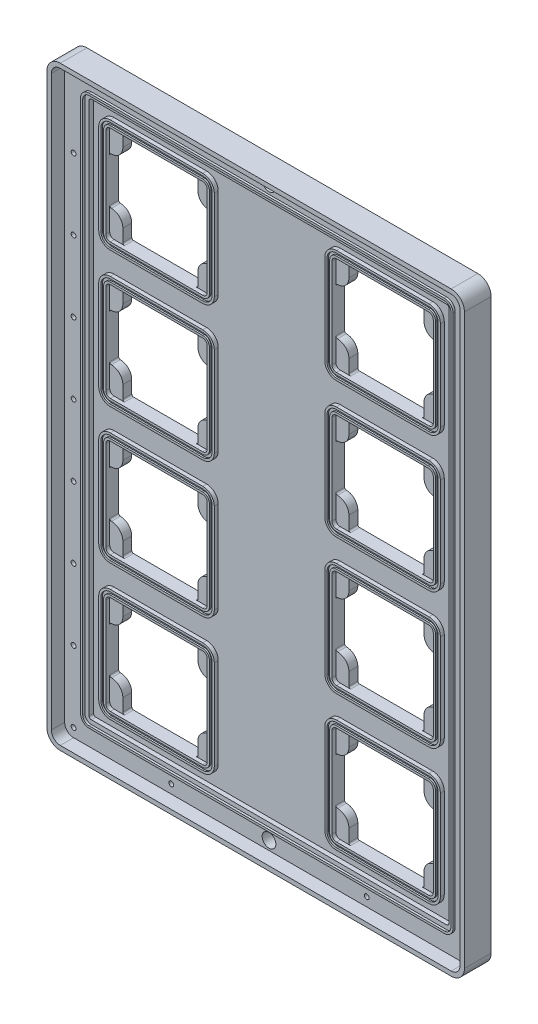
SolidWorks part; units mm, degrees
ref_plane "Front Plane" through (0, 0, 0) normal (0, 0, 1) x (1, 0, 0)
ref_plane "Top Plane" through (0, 0, 0) normal (0, 1, 0) x (1, 0, 0)
ref_plane "Right Plane" through (0, 0, 0) normal (1, 0, 0) x (0, 0, -1)
sketch "Sketch1" plane through (0, 0, 0) normal (0, 0, 1) x (1, 0, 0)
  line L1 (0, 0) -> (292.1, 0)
  line L2 (0, 0) -> (0, 419.1)
  line L3 (0, 419.1) -> (292.1, 419.1)
  line L4 (292.1, 0) -> (292.1, 419.1)
  dimension "D1" = 419.1
  dimension "D2" = 292.1
extrude "Boss-Extrude1" add sketch "Sketch1" along normal blind 9.525
sketch "Sketch4" plane through (0, 0, 9.525) normal (0, 0, 1) x (1, 0, 0)
  line L3 (0, 419.1) -> (0, 0) construction
  line L4 (6.35, 412.75) -> (285.75, 412.75) construction
  line L5 (6.35, 412.75) -> (6.35, 6.35) construction
  line L6 (6.35, 6.35) -> (285.75, 6.35) construction
  line L7 (285.75, 412.75) -> (285.75, 6.35) construction
  line L8 (292.1, 419.1) -> (0, 419.1) construction
  line L9 (292.1, 0) -> (292.1, 419.1) construction
  line L10 (0, 0) -> (292.1, 0) construction
  circle A0 centre (6.35, 6.35) radius 1.7272
  circle A1 centre (6.35, 412.75) radius 1.7272
  circle A2 centre (285.75, 412.75) radius 1.7272
  circle A3 centre (285.75, 6.35) radius 1.7272
  dimension "D5" = 3.4544
  dimension "D1" = 6.35
  dimension "D2" = 6.35
  dimension "D3" = 6.35
  dimension "D4" = 6.35
extrude "Cut-Extrude1" cut sketch "Sketch4" against normal blind 6.985
pattern_linear "LPattern2" count 8 spacing 50.8 along (0, -1, 0) of "Cut-Extrude1"
pattern_linear "LPattern3" count 4 spacing 69.85 along (-1, 0, 0) of "Cut-Extrude1"
sketch "Sketch5" plane through (0, 0, 9.525) normal (0, 0, 1) x (1, 0, 0)
  line L0 (0, 419.1) -> (0, 0) construction
  line L1 (19.05, 406.4) -> (273.05, 406.4) construction
  line L2 (12.7, 400.05) -> (12.7, 19.05) construction
  line L3 (19.05, 12.7) -> (273.05, 12.7) construction
  line L4 (279.4, 400.05) -> (279.4, 19.05) construction
  line L5 (292.1, 419.1) -> (0, 419.1) construction
  line L6 (292.1, 0) -> (292.1, 419.1) construction
  line L7 (0, 0) -> (292.1, 0) construction
  line L8 (19.05, 14.732) -> (273.05, 14.732) construction
  line L9 (14.732, 400.05) -> (14.732, 19.05) construction
  line L10 (19.05, 404.368) -> (273.05, 404.368) construction
  line L11 (277.368, 400.05) -> (277.368, 19.05) construction
  line L12 (12.954, 400.05) -> (12.954, 19.05)
  line L13 (19.05, 406.146) -> (273.05, 406.146)
  line L14 (279.146, 400.05) -> (279.146, 19.05)
  line L15 (19.05, 12.954) -> (273.05, 12.954)
  line L16 (277.622, 400.05) -> (277.622, 19.05)
  line L17 (19.05, 404.622) -> (273.05, 404.622)
  line L18 (14.478, 400.05) -> (14.478, 19.05)
  line L19 (19.05, 14.478) -> (273.05, 14.478)
  arc A0 (273.05, 12.7) -> (279.4, 19.05) centre (273.05, 19.05) ccw construction
  arc A1 (12.7, 19.05) -> (19.05, 12.7) centre (19.05, 19.05) ccw construction
  arc A2 (273.05, 406.4) -> (279.4, 400.05) centre (273.05, 400.05) cw construction
  arc A3 (19.05, 406.4) -> (12.7, 400.05) centre (19.05, 400.05) ccw construction
  arc A4 (14.732, 19.05) -> (19.05, 14.732) centre (19.05, 19.05) ccw construction
  arc A5 (19.05, 404.368) -> (14.732, 400.05) centre (19.05, 400.05) ccw construction
  arc A6 (273.05, 404.368) -> (277.368, 400.05) centre (273.05, 400.05) cw construction
  arc A7 (273.05, 14.732) -> (277.368, 19.05) centre (273.05, 19.05) ccw construction
  arc A8 (19.05, 406.146) -> (12.954, 400.05) centre (19.05, 400.05) ccw
  arc A9 (273.05, 406.146) -> (279.146, 400.05) centre (273.05, 400.05) cw
  arc A10 (273.05, 12.954) -> (279.146, 19.05) centre (273.05, 19.05) ccw
  arc A11 (12.954, 19.05) -> (19.05, 12.954) centre (19.05, 19.05) ccw
  arc A12 (273.05, 404.622) -> (277.622, 400.05) centre (273.05, 400.05) cw
  arc A13 (19.05, 404.622) -> (14.478, 400.05) centre (19.05, 400.05) ccw
  arc A14 (14.478, 19.05) -> (19.05, 14.478) centre (19.05, 19.05) ccw
  arc A15 (273.05, 14.478) -> (277.622, 19.05) centre (273.05, 19.05) ccw
  dimension "D5" = 6.35
  dimension "D1" = 12.7
  dimension "D2" = 12.7
  dimension "D3" = 12.7
  dimension "D4" = 12.7
  dimension "D6" = 2.032
  dimension "D7" = 2.032
  dimension "D8" = 0.254
  dimension "D9" = 0.254
  dimension "D10" = 0.254
sketch "Sketch6" plane through (0, 0, 9.525) normal (0, 0, 1) x (1, 0, 0)
  line L0 (292.1, 419.1) -> (0, 419.1) construction
  line L1 (0, 419.1) -> (0, 0) construction
  line L24 (273.05, 401.6375) -> (19.05, 401.6375)
  line L25 (274.6375, 19.05) -> (274.6375, 400.05)
  line L26 (19.05, 17.4625) -> (273.05, 17.4625)
  line L27 (17.4625, 400.05) -> (17.4625, 19.05)
  line L28 (273.05, 401.6375) -> (19.05, 401.6375)
  line L29 (274.6375, 19.05) -> (274.6375, 400.05)
  line L30 (19.05, 17.4625) -> (273.05, 17.4625)
  line L31 (17.4625, 400.05) -> (17.4625, 19.05)
  arc A20 (19.05, 401.6375) -> (17.4625, 400.05) centre (19.05, 400.05) ccw
  arc A21 (274.6375, 400.05) -> (273.05, 401.6375) centre (273.05, 400.05) ccw
  arc A22 (273.05, 17.4625) -> (274.6375, 19.05) centre (273.05, 19.05) ccw
  arc A23 (17.4625, 19.05) -> (19.05, 17.4625) centre (19.05, 19.05) ccw
  arc A24 (19.05, 401.6375) -> (17.4625, 400.05) centre (19.05, 400.05) ccw
  arc A25 (274.6375, 400.05) -> (273.05, 401.6375) centre (273.05, 400.05) ccw
  arc A26 (273.05, 17.4625) -> (274.6375, 19.05) centre (273.05, 19.05) ccw
  arc A27 (17.4625, 19.05) -> (19.05, 17.4625) centre (19.05, 19.05) ccw
  dimension "D2" = 17.4625
  dimension "D3" = 17.4625
  dimension "D1" = 2.7305
extrude "Cut-Extrude3" cut sketch "Sketch6" against normal blind 3.175
extrude "Boss-Extrude2" add sketch "Sketch5" along normal blind 1.5875 contours L12 A11 L15 A10 L14 A9 L13 A8 A15 L19 A14 L18 A13 L17 A12 L16 region at (15.0752, 404.0248, 9.525)
sketch "Sketch7" plane through (0, 0, 9.525) normal (0, 0, 1) x (1, 0, 0)
  circle A0 centre (146.05, 6.35) radius 4.9022
  circle A1 centre (146.05, 412.75) radius 4.9022
  dimension "D1" = 9.8044
extrude "Cut-Extrude4" cut sketch "Sketch7" against normal through all
fillet "Fillet1" radius 6.35 4 edges at (0, 419.1, 4.7625) (292.1, 419.1, 4.7625) (0, 0, 4.7625) (292.1, 0, 4.7625)
sketch "Sketch8" plane through (0, 0, 0) normal (0, 0, -1) x (-1, 0, 0)
  line L0 (-264.668, 370.459) -> (-264.668, 339.2678)
  line L1 (-255.27, 329.8698) -> (-255.27, 320.8782)
  line L2 (-252.4506, 318.0588) -> (-201.2442, 318.0588)
  line L3 (-198.4248, 320.8782) -> (-198.4248, 329.8698)
  line L4 (-189.0268, 339.2678) -> (-189.0268, 370.459)
  line L5 (-198.4248, 379.857) -> (-198.4248, 388.8486)
  line L6 (-201.2442, 391.668) -> (-252.4506, 391.668)
  line L7 (-255.27, 388.8486) -> (-255.27, 379.857)
  line L8 (-261.8486, 391.668) -> (-261.8486, 318.0588) construction
  line L9 (-264.668, 388.8486) -> (-189.0268, 388.8486) construction
  line L10 (-264.668, 391.668) -> (-189.0268, 391.668) construction
  line L11 (-264.668, 391.668) -> (-264.668, 318.0588) construction
  line L12 (-264.668, 318.0588) -> (-189.0268, 318.0588) construction
  line L13 (-189.0268, 391.668) -> (-189.0268, 318.0588) construction
  line L14 (-264.668, 379.857) -> (-189.0268, 379.857) construction
  line L15 (-264.668, 370.459) -> (-189.0268, 370.459) construction
  line L16 (-264.668, 339.2678) -> (-189.0268, 339.2678) construction
  line L17 (-264.668, 329.8698) -> (-189.0268, 329.8698) construction
  line L18 (-264.668, 320.8782) -> (-189.0268, 320.8782) construction
  line L19 (-255.27, 318.0588) -> (-255.27, 391.668) construction
  line L20 (-252.4506, 391.668) -> (-252.4506, 318.0588) construction
  line L21 (-201.2442, 391.668) -> (-201.2442, 318.0588) construction
  line L22 (-198.4248, 391.668) -> (-198.4248, 318.0588) construction
  line L23 (-191.8462, 318.0588) -> (-191.8462, 391.668) construction
  line L24 (-189.0268, 373.2784) -> (-264.668, 373.2784) construction
  line L27 (-201.2442, 393.7) -> (-252.4506, 393.7)
  line L28 (-257.302, 388.8486) -> (-257.302, 379.857)
  line L29 (-266.7, 370.459) -> (-266.7, 339.2678)
  line L30 (-257.302, 329.8698) -> (-257.302, 320.8782)
  line L31 (-252.4506, 316.0268) -> (-201.2442, 316.0268)
  line L32 (-196.3928, 320.8782) -> (-196.3928, 329.8698)
  line L33 (-186.9948, 339.2678) -> (-186.9948, 370.459)
  line L34 (-196.3928, 379.857) -> (-196.3928, 388.8486)
  line L35 (-285.75, 419.1) -> (-6.35, 419.1) construction
  line L36 (-292.1, 6.35) -> (-292.1, 412.75) construction
  arc A0 (-261.8486, 373.2784) -> (-255.27, 379.857) centre (-261.8486, 379.857) ccw
  arc A1 (-261.8486, 373.2784) -> (-264.668, 370.459) centre (-261.8486, 370.459) ccw
  arc A2 (-264.668, 339.2678) -> (-261.8486, 336.4484) centre (-261.8486, 339.2678) ccw
  arc A3 (-255.27, 329.8698) -> (-261.8486, 336.4484) centre (-261.8486, 329.8698) ccw
  arc A4 (-255.27, 320.8782) -> (-252.4506, 318.0588) centre (-252.4506, 320.8782) ccw
  arc A5 (-201.2442, 318.0588) -> (-198.4248, 320.8782) centre (-201.2442, 320.8782) ccw
  arc A6 (-191.8462, 336.4484) -> (-198.4248, 329.8698) centre (-191.8462, 329.8698) ccw
  arc A7 (-191.8462, 336.4484) -> (-189.0268, 339.2678) centre (-191.8462, 339.2678) ccw
  arc A8 (-189.0268, 370.459) -> (-191.8462, 373.2784) centre (-191.8462, 370.459) ccw
  arc A9 (-198.4248, 379.857) -> (-191.8462, 373.2784) centre (-191.8462, 379.857) ccw
  arc A10 (-198.4248, 388.8486) -> (-201.2442, 391.668) centre (-201.2442, 388.8486) ccw
  arc A11 (-252.4506, 391.668) -> (-255.27, 388.8486) centre (-252.4506, 388.8486) ccw
  arc A12 (-252.4506, 393.7) -> (-257.302, 388.8486) centre (-252.4506, 388.8486) ccw
  arc A13 (-261.8486, 375.3104) -> (-257.302, 379.857) centre (-261.8486, 379.857) ccw
  arc A14 (-261.8486, 375.3104) -> (-266.7, 370.459) centre (-261.8486, 370.459) ccw
  arc A15 (-266.7, 339.2678) -> (-261.8486, 334.4164) centre (-261.8486, 339.2678) ccw
  arc A16 (-257.302, 329.8698) -> (-261.8486, 334.4164) centre (-261.8486, 329.8698) ccw
  arc A17 (-257.302, 320.8782) -> (-252.4506, 316.0268) centre (-252.4506, 320.8782) ccw
  arc A18 (-201.2442, 316.0268) -> (-196.3928, 320.8782) centre (-201.2442, 320.8782) ccw
  arc A19 (-191.8462, 334.4164) -> (-196.3928, 329.8698) centre (-191.8462, 329.8698) ccw
  arc A20 (-191.8462, 334.4164) -> (-186.9948, 339.2678) centre (-191.8462, 339.2678) ccw
  arc A21 (-186.9948, 370.459) -> (-191.8462, 375.3104) centre (-191.8462, 370.459) ccw
  arc A22 (-196.3928, 379.857) -> (-191.8462, 375.3104) centre (-191.8462, 379.857) ccw
  arc A23 (-196.3928, 388.8486) -> (-201.2442, 393.7) centre (-201.2442, 388.8486) ccw
  dimension "D4" = 11.811
  dimension "D5" = 21.209
  dimension "D6" = 52.4002
  dimension "D1" = 73.6092
  dimension "D2" = 75.6412
  dimension "D3" = 2.8194
  dimension "D7" = 61.7982
  dimension "D8" = 70.7898
  dimension "D9" = 2.8194
  dimension "D10" = 9.398
  dimension "D11" = 12.2174
  dimension "D12" = 63.4238
  dimension "D13" = 66.2432
  dimension "D14" = 72.8218
  dimension "D15" = 55.2196
  dimension "D16" = 25.4
  dimension "D17" = 25.4
  dimension "D18" = 2.032
extrude "Cut-Extrude5" cut sketch "Sketch8" against normal blind 3.175
sketch "Sketch10" plane through (0, 0, 0) normal (0, 0, -1) x (-1, 0, 0)
  line L18 (-263.0805, 370.459) -> (-263.0805, 339.2678)
  line L19 (-253.6825, 329.8698) -> (-253.6825, 320.8782)
  line L20 (-252.4506, 319.6463) -> (-201.2442, 319.6463)
  line L21 (-200.0123, 320.8782) -> (-200.0123, 329.8698)
  line L22 (-190.6143, 339.2678) -> (-190.6143, 370.459)
  line L23 (-200.0123, 379.857) -> (-200.0123, 388.8486)
  line L24 (-201.2442, 390.0805) -> (-252.4506, 390.0805)
  line L25 (-253.6825, 388.8486) -> (-253.6825, 379.857)
  line L26 (-263.0805, 370.459) -> (-263.0805, 339.2678)
  line L27 (-253.6825, 329.8698) -> (-253.6825, 320.8782)
  line L28 (-252.4506, 319.6463) -> (-201.2442, 319.6463)
  line L29 (-200.0123, 320.8782) -> (-200.0123, 329.8698)
  line L30 (-190.6143, 339.2678) -> (-190.6143, 370.459)
  line L31 (-200.0123, 379.857) -> (-200.0123, 388.8486)
  line L32 (-201.2442, 390.0805) -> (-252.4506, 390.0805)
  line L33 (-253.6825, 388.8486) -> (-253.6825, 379.857)
  arc A28 (-261.8486, 371.6909) -> (-263.0805, 370.459) centre (-261.8486, 370.459) ccw
  arc A29 (-263.0805, 339.2678) -> (-261.8486, 338.0359) centre (-261.8486, 339.2678) ccw
  arc A30 (-253.6825, 329.8698) -> (-261.8486, 338.0359) centre (-261.8486, 329.8698) ccw
  arc A31 (-253.6825, 320.8782) -> (-252.4506, 319.6463) centre (-252.4506, 320.8782) ccw
  arc A32 (-201.2442, 319.6463) -> (-200.0123, 320.8782) centre (-201.2442, 320.8782) ccw
  arc A33 (-191.8462, 338.0359) -> (-200.0123, 329.8698) centre (-191.8462, 329.8698) ccw
  arc A34 (-191.8462, 338.0359) -> (-190.6143, 339.2678) centre (-191.8462, 339.2678) ccw
  arc A35 (-190.6143, 370.459) -> (-191.8462, 371.6909) centre (-191.8462, 370.459) ccw
  arc A36 (-200.0123, 379.857) -> (-191.8462, 371.6909) centre (-191.8462, 379.857) ccw
  arc A37 (-200.0123, 388.8486) -> (-201.2442, 390.0805) centre (-201.2442, 388.8486) ccw
  arc A38 (-252.4506, 390.0805) -> (-253.6825, 388.8486) centre (-252.4506, 388.8486) ccw
  arc A39 (-261.8486, 371.6909) -> (-253.6825, 379.857) centre (-261.8486, 379.857) ccw
  arc A40 (-261.8486, 371.6909) -> (-263.0805, 370.459) centre (-261.8486, 370.459) ccw
  arc A41 (-263.0805, 339.2678) -> (-261.8486, 338.0359) centre (-261.8486, 339.2678) ccw
  arc A42 (-253.6825, 329.8698) -> (-261.8486, 338.0359) centre (-261.8486, 329.8698) ccw
  arc A43 (-253.6825, 320.8782) -> (-252.4506, 319.6463) centre (-252.4506, 320.8782) ccw
  arc A44 (-201.2442, 319.6463) -> (-200.0123, 320.8782) centre (-201.2442, 320.8782) ccw
  arc A45 (-191.8462, 338.0359) -> (-200.0123, 329.8698) centre (-191.8462, 329.8698) ccw
  arc A46 (-191.8462, 338.0359) -> (-190.6143, 339.2678) centre (-191.8462, 339.2678) ccw
  arc A47 (-190.6143, 370.459) -> (-191.8462, 371.6909) centre (-191.8462, 370.459) ccw
  arc A48 (-200.0123, 379.857) -> (-191.8462, 371.6909) centre (-191.8462, 379.857) ccw
  arc A49 (-200.0123, 388.8486) -> (-201.2442, 390.0805) centre (-201.2442, 388.8486) ccw
  arc A50 (-252.4506, 390.0805) -> (-253.6825, 388.8486) centre (-252.4506, 388.8486) ccw
  arc A51 (-261.8486, 371.6909) -> (-253.6825, 379.857) centre (-261.8486, 379.857) ccw
  dimension "D1" = 1.5875
extrude "Cut-Extrude6" cut sketch "Sketch10" against normal through all
sketch "Sketch11" plane through (0, 0, 0) normal (0, 0, -1) x (-1, 0, 0)
  line L0 (-226.8474, 388.8994) -> (-226.8474, 393.7) construction
  line L1 (-261.8486, 388.8994) -> (-191.8462, 388.8994) construction
  line L2 (-261.8486, 388.8994) -> (-261.8486, 320.8274) construction
  line L3 (-261.8486, 320.8274) -> (-191.8462, 320.8274) construction
  line L4 (-191.8462, 388.8994) -> (-191.8462, 320.8274) construction
  line L5 (-201.2442, 393.7) -> (-252.4506, 393.7) construction
  line L6 (-226.8474, 320.8274) -> (-226.8474, 316.0268) construction
  line L7 (-252.4506, 316.0268) -> (-201.2442, 316.0268) construction
  line L8 (-261.8486, 354.8634) -> (-266.7, 354.8634) construction
  line L9 (-266.7, 370.459) -> (-266.7, 339.2678) construction
  line L10 (-191.8462, 354.8634) -> (-186.9948, 354.8634) construction
  line L11 (-186.9948, 339.2678) -> (-186.9948, 370.459) construction
  circle A0 centre (-261.8486, 388.8994) radius 1.1303
  circle A1 centre (-191.8462, 388.8994) radius 1.1303
  circle A2 centre (-191.8462, 320.8274) radius 1.1303
  circle A3 centre (-261.8486, 320.8274) radius 1.1303
  dimension "D3" = 2.2606
  dimension "D1" = 70.0024
  dimension "D2" = 68.072
extrude "Cut-Extrude7" cut sketch "Sketch11" against normal blind 3.9688
sketch "Sketch12" plane through (0, 0, 6.35) normal (0, 0, 1) x (1, 0, 0)
  line L0 (252.4506, 390.0805) -> (201.2442, 390.0805) construction
  line L1 (193.7893, 390.0805) -> (259.9055, 390.0805)
  line L2 (190.6143, 386.9055) -> (190.6143, 322.8213)
  line L3 (193.7893, 319.6463) -> (259.9055, 319.6463)
  line L4 (263.0805, 386.9055) -> (263.0805, 322.8213)
  line L5 (263.0805, 339.2678) -> (263.0805, 370.459) construction
  line L10 (193.7893, 391.668) -> (259.9055, 391.668)
  line L11 (264.668, 386.9055) -> (264.668, 322.8213)
  line L12 (193.7893, 318.0588) -> (259.9055, 318.0588)
  line L13 (189.0268, 386.9055) -> (189.0268, 322.8213)
  line L14 (187.1218, 386.9055) -> (187.1218, 322.8213)
  line L15 (193.7893, 316.1538) -> (259.9055, 316.1538)
  line L16 (266.573, 386.9055) -> (266.573, 322.8213)
  line L17 (193.7893, 393.573) -> (259.9055, 393.573)
  line L18 (185.5343, 386.9055) -> (185.5343, 322.8213)
  line L19 (193.7893, 314.5663) -> (259.9055, 314.5663)
  line L20 (268.1605, 386.9055) -> (268.1605, 322.8213)
  line L21 (193.7893, 395.1605) -> (259.9055, 395.1605)
  line L22 (201.2442, 319.6463) -> (252.4506, 319.6463) construction
  line L23 (190.6143, 370.459) -> (190.6143, 339.2678) construction
  arc A0 (259.9055, 319.6463) -> (263.0805, 322.8213) centre (259.9055, 322.8213) ccw
  arc A1 (190.6143, 322.8213) -> (193.7893, 319.6463) centre (193.7893, 322.8213) ccw
  arc A2 (259.9055, 390.0805) -> (263.0805, 386.9055) centre (259.9055, 386.9055) cw
  arc A3 (193.7893, 390.0805) -> (190.6143, 386.9055) centre (193.7893, 386.9055) ccw
  arc A4 (259.9055, 391.668) -> (264.668, 386.9055) centre (259.9055, 386.9055) cw
  arc A5 (259.9055, 318.0588) -> (264.668, 322.8213) centre (259.9055, 322.8213) ccw
  arc A6 (189.0268, 322.8213) -> (193.7893, 318.0588) centre (193.7893, 322.8213) ccw
  arc A7 (193.7893, 391.668) -> (189.0268, 386.9055) centre (193.7893, 386.9055) ccw
  arc A8 (187.1218, 322.8213) -> (193.7893, 316.1538) centre (193.7893, 322.8213) ccw
  arc A9 (259.9055, 316.1538) -> (266.573, 322.8213) centre (259.9055, 322.8213) ccw
  arc A10 (259.9055, 393.573) -> (266.573, 386.9055) centre (259.9055, 386.9055) cw
  arc A11 (193.7893, 393.573) -> (187.1218, 386.9055) centre (193.7893, 386.9055) ccw
  arc A12 (185.5343, 322.8213) -> (193.7893, 314.5663) centre (193.7893, 322.8213) ccw
  arc A13 (259.9055, 314.5663) -> (268.1605, 322.8213) centre (259.9055, 322.8213) ccw
  arc A14 (259.9055, 395.1605) -> (268.1605, 386.9055) centre (259.9055, 386.9055) cw
  arc A15 (193.7893, 395.1605) -> (185.5343, 386.9055) centre (193.7893, 386.9055) ccw
  dimension "D1" = 3.175
  dimension "D2" = 1.5875
  dimension "D3" = 1.905
  dimension "D4" = 1.5875
extrude "Boss-Extrude3" add sketch "Sketch12" along normal blind 2.794 contours L21 A15 L18 A12 L19 A13 L20 A14 A11 L17 A10 L16 A9 L15 A8 L14 | L10 A7 L13 A6 L12 A5 L11 A4 A3 L1 A2 L4 A0 L3 A1 L2 region at (226.8474, 390.6125, 6.35) region at (188.7683, 391.9265, 6.35)
extrude "Boss-Extrude4" add sketch "Sketch12<3>" along normal blind 1.651 contours L17 A11 L14 A8 L15 A9 L16 A10 A7 L10 A4 L11 A5 L12 A6 L13 region at (189.8591, 390.8357, 6.35)
sketch "Sketch12<3>" plane through (0, 0, 6.35) normal (0, 0, 1) x (1, 0, 0) same geometry as "Sketch12"
pattern_linear "LPattern1" count 2 spacing 161.5948 along (-1, 0, 0) count 4 spacing 96.8756 along (0, -1, 0) of "Cut-Extrude6", "Cut-Extrude5", "Cut-Extrude7", "Boss-Extrude3", "Boss-Extrude4"
sketch "Sketch13" plane through (0, 0, 0) normal (0, 0, -1) x (-1, 0, 0)
  line L4 (-6.35, 419.1) -> (-285.75, 419.1)
  line L5 (-292.1, 412.75) -> (-292.1, 6.35)
  line L6 (-285.75, 0) -> (-6.35, 0)
  line L7 (0, 6.35) -> (0, 412.75)
  line L8 (-285.75, -3.175) -> (-6.35, -3.175)
  line L9 (3.175, 6.35) -> (3.175, 412.75)
  line L10 (-6.35, 422.275) -> (-285.75, 422.275)
  line L11 (-295.275, 412.75) -> (-295.275, 6.35)
  line L12 (-285.75, -3.175) -> (-6.35, -3.175)
  line L13 (3.175, 6.35) -> (3.175, 412.75)
  line L14 (-6.35, 422.275) -> (-285.75, 422.275)
  line L15 (-295.275, 412.75) -> (-295.275, 6.35)
  arc A4 (-285.75, 419.1) -> (-292.1, 412.75) centre (-285.75, 412.75) ccw
  arc A5 (-292.1, 6.35) -> (-285.75, 0) centre (-285.75, 6.35) ccw
  arc A6 (-6.35, 0) -> (0, 6.35) centre (-6.35, 6.35) ccw
  arc A7 (0, 412.75) -> (-6.35, 419.1) centre (-6.35, 412.75) ccw
  arc A8 (-295.275, 6.35) -> (-285.75, -3.175) centre (-285.75, 6.35) ccw
  arc A9 (-6.35, -3.175) -> (3.175, 6.35) centre (-6.35, 6.35) ccw
  arc A10 (3.175, 412.75) -> (-6.35, 422.275) centre (-6.35, 412.75) ccw
  arc A11 (-285.75, 422.275) -> (-295.275, 412.75) centre (-285.75, 412.75) ccw
  arc A12 (-295.275, 6.35) -> (-285.75, -3.175) centre (-285.75, 6.35) ccw
  arc A13 (-6.35, -3.175) -> (3.175, 6.35) centre (-6.35, 6.35) ccw
  arc A14 (3.175, 412.75) -> (-6.35, 422.275) centre (-6.35, 412.75) ccw
  arc A15 (-285.75, 422.275) -> (-295.275, 412.75) centre (-285.75, 412.75) ccw
  dimension "D1" = 3.175
  dimension "D2" = 3.175
extrude "Boss-Extrude5" add sketch "Sketch13" against normal blind 19.05
